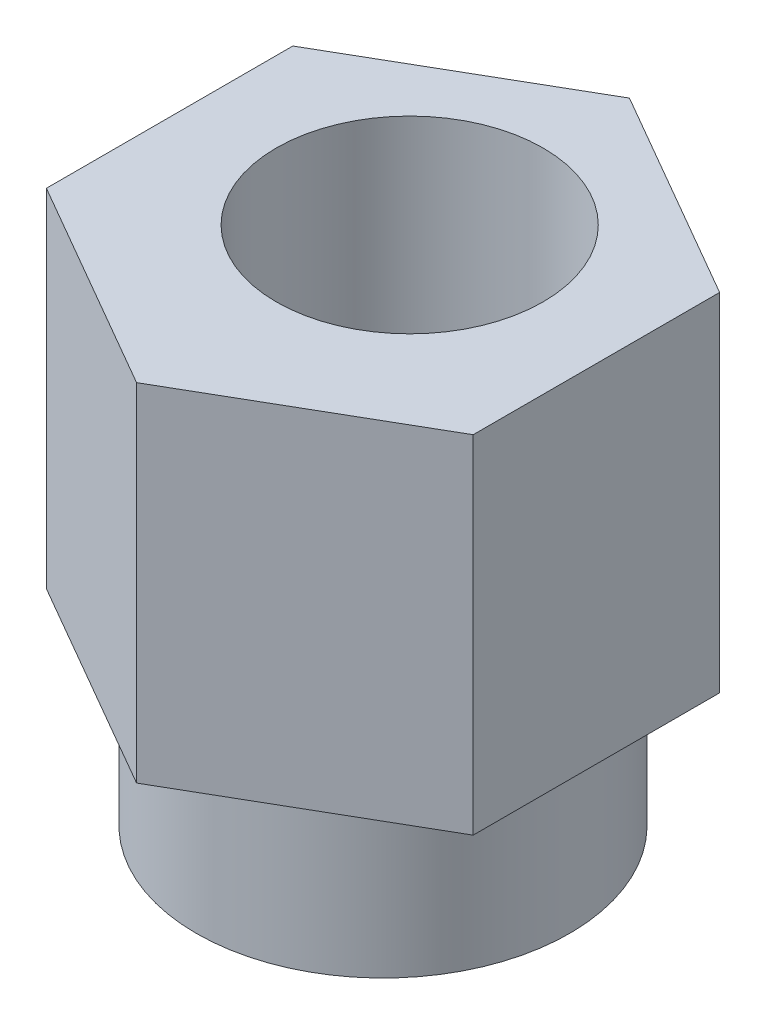
SolidWorks part; units mm, degrees
ref_plane "Спереди" through (0, 0, 0) normal (0, 0, 1) x (1, 0, 0)
ref_plane "Сверху" through (0, 0, 0) normal (0, 1, 0) x (1, 0, 0)
ref_plane "Справа" through (0, 0, 0) normal (1, 0, 0) x (0, 0, -1)
sketch "Эскиз1" plane through (0, 0, 0) normal (0, 1, 0) x (1, 0, 0)
  line L0 (-4, 0) -> (4, 0) construction
  line L1 (0, -4.6188) -> (4, -2.3094)
  line L2 (4, -2.3094) -> (4, 2.3094)
  line L3 (4, 2.3094) -> (0, 4.6188)
  line L4 (0, 4.6188) -> (-4, 2.3094)
  line L5 (-4, 2.3094) -> (-4, -2.3094)
  line L6 (-4, -2.3094) -> (0, -4.6188)
  circle A0 centre (0, 0) radius 4 construction
  dimension "D1" = 8
extrude "Бобышка-Вытянуть1" add sketch "Эскиз1" along normal blind 6.5
sketch "Эскиз2" plane through (0, 0, 0) normal (0, 1, 0) x (1, 0, 0)
  line L0 (0, 0) -> (0, 0.5) construction
  circle A0 centre (0, 0) radius 3.5
  circle A1 centre (0, 0.5) radius 2.5
  dimension "D1" = 7
  dimension "D3" = 5
  dimension "D2" = 0.5
extrude "Бобышка-Вытянуть2" add sketch "Эскиз2" against normal blind 3
extrude "Вырез-Вытянуть1" cut sketch "Эскиз2<2>" along normal through all contours A1 region at (0, 0, -0.5)
sketch "Эскиз2<2>" plane through (0, 0, 0) normal (0, 1, 0) x (1, 0, 0) same geometry as "Эскиз2"
